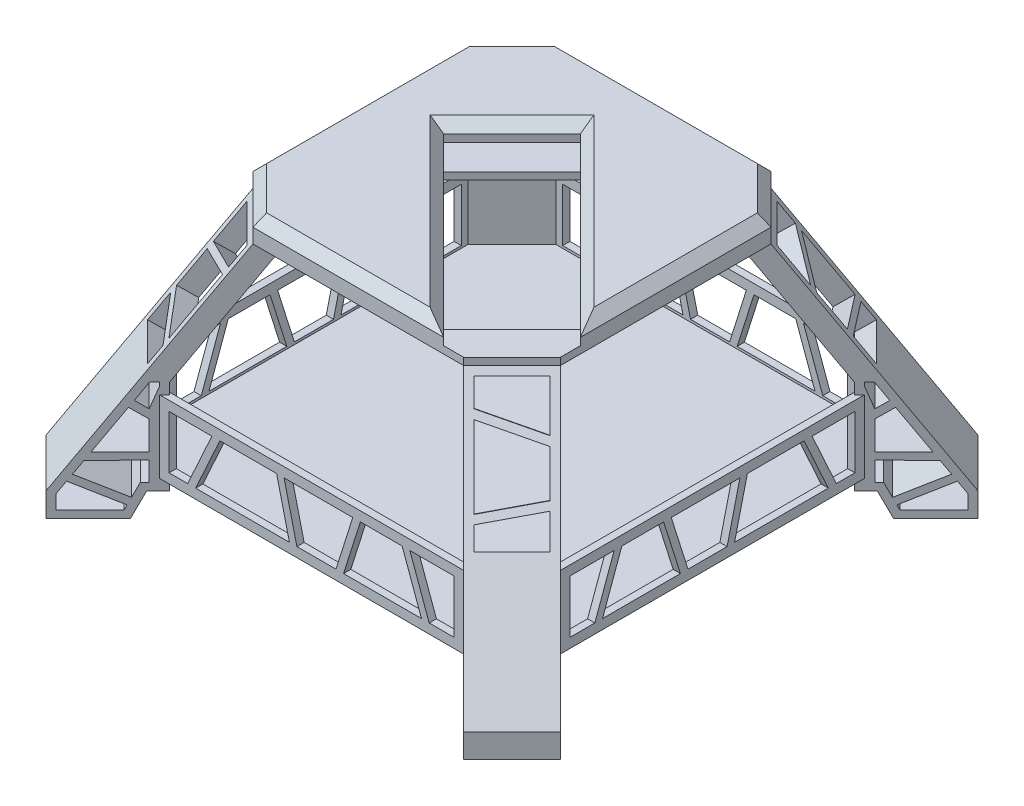
SolidWorks part; units mm, degrees
ref_plane "Front Plane" through (0, 0, 0) normal (0, 0, 1) x (1, 0, 0)
ref_plane "Top Plane" through (0, 0, 0) normal (0, 1, 0) x (1, 0, 0)
ref_plane "Right Plane" through (0, 0, 0) normal (1, 0, 0) x (0, 0, -1)
sketch "Sketch1" plane through (0, 0, 0) normal (0, 1, 0) x (1, 0, 0)
  line L0 (-31.5, 41.5) -> (-41.5, 31.5)
  line L1 (-31.5, 41.5) -> (31.5, 41.5)
  line L2 (-41.5, 31.5) -> (-41.5, -31.5)
  line L3 (-31.5, -41.5) -> (31.5, -41.5)
  line L4 (41.5, 31.5) -> (41.5, -31.5)
  line L5 (-41.5, 41.5) -> (41.5, -41.5) construction
  line L6 (-41.5, -41.5) -> (41.5, 41.5) construction
  line L7 (31.5, 41.5) -> (41.5, 31.5)
  line L8 (41.5, -31.5) -> (31.5, -41.5)
  line L9 (-41.5, -31.5) -> (-31.5, -41.5)
  point P0 (0, 0)
  point P14 (40, -37.4819)
  dimension "D1" = 83
extrude "Boss-Extrude1" add sketch "Sketch1" along normal blind 15
shell "Shell1" thickness 1.5 removed face at (0, 15, 0)
ref_plane "Plane1" through (0, 0, 0) normal (-0.7071, 0, 0.7071) x (0.7071, 0, 0.7071)
sketch "Sketch15" plane through (41.5, 0, 0) normal (1, 0, 0) x (0, 0, -1)
  line L0 (18.9934, 13) -> (7.2371, 13)
  line L1 (25.6494, 2) -> (29.5, 2)
  line L4 (-24.3478, 2) -> (-20.3494, 13)
  line L5 (-22.7518, 2) -> (-18.7534, 13)
  line L6 (-10.1007, 13) -> (-6.6274, 2)
  line L7 (-8.5277, 13) -> (-5.0544, 2)
  line L8 (-29.5, 2) -> (29.5, 2)
  line L9 (29.5, 2) -> (29.5, 13)
  line L10 (29.5, 13) -> (-29.5, 13)
  line L11 (-29.5, 13) -> (-29.5, 2)
  line L12 (-29.5, 2) -> (-24.3478, 2)
  line L13 (29.5, 2) -> (29.5, 13)
  line L14 (29.5, 13) -> (20.6415, 13)
  line L15 (-29.5, 13) -> (-29.5, 2)
  line L16 (5.6941, 13) -> (3.0427, 2)
  line L17 (7.2371, 13) -> (4.5856, 2)
  line L18 (20.6415, 13) -> (25.6494, 2)
  line L19 (18.9934, 13) -> (24.0013, 2)
  line L20 (-10.1007, 13) -> (-18.7534, 13)
  line L21 (-5.0544, 2) -> (3.0427, 2)
  line L22 (-22.7518, 2) -> (-6.6274, 2)
  line L23 (-20.3494, 13) -> (-29.5, 13)
  line L24 (5.6941, 13) -> (-8.5277, 13)
  line L25 (4.5856, 2) -> (24.0013, 2)
  point P20 (-22.805, 13.5)
  point P21 (-12.8485, 13.5)
  point P22 (-18.7519, 13.5)
  point P23 (-6.6279, 1.5)
  point P24 (2.6342, 1.5)
  point P25 (7.646, 13.5)
  point P26 (24.2021, 1.5)
  point P27 (16.3093, 13.5)
  point P28 (-10.1007, 13)
  point P29 (5.6941, 13)
  point P30 (20.6415, 13)
  dimension "D2" = 1.5
  dimension "D3" = 1.5
  dimension "D4" = 1.5
  dimension "D5" = 1.5
extrude "Cut-Extrude3" cut sketch "Sketch15" against normal through all
mirror "Mirror4" about plane through (0, 0, 0) normal (-0.7071, 0, 0.7071) of "Cut-Extrude3"
sketch "Sketch2" plane through (0, 0, 0) normal (-0.7071, 0, 0.7071) x (0.7071, 0, 0.7071)
  line L8 (51.6188, 15) -> (50.1188, 15)
  line L9 (7.0711, 15) -> (51.6188, 15) construction
  line L10 (50.1188, 15) -> (50.1188, 17.2822)
  line L11 (50.1188, 17.2822) -> (54.873, 17.2822)
  line L12 (54.873, 17.2822) -> (68.2293, -2.2291)
  line L13 (68.2293, -2.2291) -> (68.2293, -7.1547)
  line L15 (68.2293, -7.1547) -> (55.8508, -7.1547)
  line L16 (55.8508, -7.1547) -> (53.4827, -2.2291)
  line L17 (53.4827, -2.2291) -> (50.1188, -2.2291)
  line L18 (50.1188, -2.2291) -> (50.1188, 0)
  line L19 (7.0711, 0) -> (51.6188, 0) construction
  line L20 (50.1188, 0) -> (51.6188, 0)
  line L21 (51.6188, 0) -> (51.6188, 15)
  point P2 (64.5609, -7.0719)
  point P3 (62.5346, -7.0719)
  point P6 (56.9209, -7.2687)
  point P10 (0, 0)
  point P21 (52.5181, -4.5307)
  point P22 (0, 0)
  point P23 (78.9484, -7.599)
  point P24 (57.923, -7.599)
  point P25 (68.246, 13.75)
  point P26 (71.077, 1.0103)
  point P27 (69.9761, 12.649)
  point P28 (77.9974, 1.3248)
  point P29 (77.9974, -7.9547)
  point P30 (50.7878, -12.044)
  point P31 (57.5509, -13.3023)
  point P32 (58.6405, 20.9849)
  point P33 (75.6382, 12.1772)
  point P34 (75.6382, -7.4459)
  point P35 (54.248, -3.7082)
  point P36 (74.7081, 6.8297)
  point P37 (61.6402, -7.4459)
  point P38 (58.0112, -3.0389)
  point P39 (0, 0)
  point P40 (0, 0)
  point P41 (46.258, 21.307)
  point P42 (65.0866, -7.4459)
  point P43 (74.3882, -0.0167)
  point P44 (48.0794, 15)
  point P45 (48.755, 15)
  point P46 (48.1238, 15)
  point P47 (0, 0)
  point P49 (48.2026, -0.5309)
  point P50 (54.4571, -7.4459)
  point P51 (51.287, -5.6451)
  point P52 (51.8837, -7.4459)
  point P53 (74.2619, -4.6657)
  point P54 (53.5036, -8.1413)
  point P55 (51.6286, -3.6276)
  point P56 (54.0935, -7.4459)
  point P57 (50.1188, 16.8913)
  point P58 (62.3577, -7.4459)
  point P59 (70.8334, -2.7865)
  point P60 (70.8334, -7.4459)
  point P61 (61.9116, -7.4459)
  point P62 (55.5176, -1.8943)
  point P63 (57.5224, -7.4459)
  point P64 (0, 0)
  point P65 (55.8508, -7.1547)
  point P66 (53.4827, -2.2291)
  point P67 (68.2293, -7.1547)
  point P68 (68.2293, -2.2291)
  point P69 (54.873, 17.2822)
extrude "Boss-Extrude2" add sketch "Sketch2" along normal up to vertex (7.0711 mm away) and the other way up to vertex (7.0711 mm away) separate body up to point (31.5, 15, 41.5) other way up to point (41.5, 15, 31.5)
sketch "Sketch6" plane through (0, 17.2822, 0) normal (0, 1, 0) x (1, 0, 0)
  line L4 (33.8011, -43.8011) -> (43.8011, -33.8011)
  line L5 (43.8011, -33.8011) -> (40.4393, -30.4393)
  line L6 (40.4393, -30.4393) -> (30.4393, -40.4393)
  line L7 (30.4393, -40.4393) -> (33.8011, -43.8011)
  line L8 (33.8011, -43.8011) -> (43.8011, -33.8011)
  line L9 (43.8011, -33.8011) -> (40.4393, -30.4393)
  line L10 (40.4393, -30.4393) -> (30.4393, -40.4393)
  line L11 (30.4393, -40.4393) -> (33.8011, -43.8011)
  dimension "D1" = 0
extrude "Boss-Extrude4" add sketch "Sketch6" along direction (-0.3994, 0.8252, -0.3994) on the side of the normal blind 30
sketch "Sketch8" plane through (32.1166, 31.0918, 32.1166) normal (0.5835, 0.5649, 0.5835) x (0.809, -0.4673, -0.3566)
  line L0 (1.1, -11.4379) -> (3.3653, -14.7346)
  line L1 (8.2873, -2.2233) -> (3.7894, 4.3224)
  line L2 (2.8883, 5.6338) -> (-2.0712, 12.8513)
  line L3 (-7.6275, 1.2631) -> (0.2369, -10.1819)
  line L4 (-8.5286, 2.5745) -> (2.8883, 5.6338)
  line L5 (-7.6275, 1.2631) -> (3.7894, 4.3224)
  line L6 (0.2369, -10.1819) -> (8.2873, -2.2233)
  line L7 (1.1, -11.4379) -> (9.1504, -3.4793)
  line L8 (17.4277, -35.1992) -> (26.6107, -28.889)
  line L9 (26.6107, -28.889) -> (-2.0712, 12.8513)
  line L10 (-2.0712, 12.8513) -> (-11.2543, 6.5411)
  line L11 (-11.2543, 6.5411) -> (17.4277, -35.1992)
  line L14 (-2.0712, 12.8513) -> (-11.2543, 6.5411)
  line L15 (-11.2543, 6.5411) -> (-8.5286, 2.5745)
  line L16 (3.3653, -14.7346) -> (12.5484, -8.4244)
  line L19 (12.5484, -8.4244) -> (9.1504, -3.4793)
  line L21 (2.1291, -15.5841) -> (13.7847, -7.5749) construction
  line L22 (28.6965, -29.2758) -> (-1.6845, 14.937) construction
  point P16 (2.1734, -12.9999)
  point P17 (6.605, 0)
  point P18 (0, -10.2448)
  point P19 (0, -9.8778)
  point P20 (-1.1516, -8.1612)
  point P21 (14.8221, -11.7333)
  point P22 (-0.3439, -9.3366)
  point P23 (11.3401, -6.666)
  point P24 (8.0094, -1.8258)
  point P25 (-6.2966, -0.6737)
  point P26 (3.8328, 4.3953)
  point P27 (-1.6692, -7.4079)
  point P28 (-1.1778, -8.4136)
  point P29 (6.7209, 0)
  point P30 (11.6875, -7.0916)
  point P31 (1.1073, -11.6826)
  point P32 (10.7464, -5.802)
  point P33 (-1.0138, -8.3617)
  point P34 (0, -10.2259)
  point P35 (9.8852, -4.5487)
  point P36 (-1.0881, -8.2535)
  point P37 (6.7776, -0.7438)
  point P38 (-0.2205, -9.5162)
  point P39 (11.7055, -7.2554)
  point P42 (8.3861, -2.3671)
  point P43 (-0.2959, -9.4064)
  point P44 (7.4734, -1.0389)
  point P45 (-0.457, -9.1721)
  point P46 (0.3662, -10.37)
  point P47 (-4.6581, -3.0582)
  point P48 (-5.069, -2.4602)
  point P49 (8.869, -3.0698)
  point P50 (0, -9.9183)
  point P51 (-4.8635, -2.7592)
  point P52 (0, -10.0166)
  point P53 (0.8274, -11.0411)
  point P54 (-4.3269, -3.5402)
  point P55 (6.729, 0)
  point P56 (-3.4368, -4.8355)
  point P57 (-4.3047, -3.5726)
  point P58 (6.246, 0.7473)
  point P59 (-3.5397, -4.8949)
  point P60 (-3.4368, -4.8355)
  point P61 (-4.3071, -3.569)
  point P62 (-4.4936, -3.2885)
  point P63 (5.4459, 1.9117)
  point P64 (-7.6565, 1.3053)
  point P65 (4.2592, 3.6387)
  point P66 (3.7894, 4.3224)
  point P67 (-7.6275, 1.2631)
  dimension "D2" = 1.5
  dimension "D3" = 1.5
  dimension "D4" = 4
  dimension "D5" = 6
  dimension "D1" = 1.5
extrude "Cut-Extrude1" cut sketch "Sketch8" against normal up to surface (3.9231 mm away) contours L14 L15 L4 L2 | L3 L6 L1 L5 | L16 L19 L7 L0 region at (36.9792, 21.5887, 36.4539) region at (32.5676, 29.4212, 33.2828) region at (29.1924, 37.9215, 28.429) up to face at (29.448, 29.6599, 29.448)
sketch "Sketch12" plane through (-5, 0, 5) normal (-0.7071, 0, 0.7071) x (0.7071, 0, 0.7071)
  line L1 (56.3607, -4.7534) -> (65.2229, -0.4927)
  line L2 (54.8346, -1.5792) -> (57.2026, -6.5047)
  line L3 (56.3607, -4.7534) -> (56.794, -5.6547)
  line L55 (51.6188, 17.2822) -> (53.0552, 17.2822)
  line L56 (53.1188, 12.4783) -> (55.3147, 13.9814)
  line L57 (53.1188, 10.6605) -> (56.162, 12.7437)
  line L58 (53.1188, 4.7709) -> (61.6416, 4.7389)
  line L59 (53.1188, 3.2709) -> (62.6711, 3.235)
  line L60 (55.7107, -3.4015) -> (64.3657, 0.7595)
  line L62 (53.1188, 10.6605) -> (53.1188, 4.7709)
  line L63 (55.3147, 13.9814) -> (53.0552, 17.2822)
  line L64 (53.1188, 3.2709) -> (53.1188, -0.7291)
  line L65 (66.7293, -2.6933) -> (36.6891, 41.1902)
  line L66 (66.7293, -5.6547) -> (66.7293, -2.6933)
  line L67 (56.794, -5.6547) -> (66.7293, -5.6547)
  line L68 (54.4259, -0.7291) -> (56.794, -5.6547)
  line L69 (51.6188, 16.5) -> (53.1188, 16.5)
  line L70 (51.6188, 17.2822) -> (51.6188, 16.5)
  line L71 (53.1188, 16.5) -> (53.1188, -0.7291)
  line L72 (53.1188, -0.7291) -> (54.4259, -0.7291)
  line L73 (66.7293, -2.6933) -> (65.2229, -0.4927)
  line L74 (66.7293, -5.6547) -> (66.7293, -2.6933)
  line L75 (56.794, -5.6547) -> (66.7293, -5.6547)
  line L76 (54.4259, -0.7291) -> (55.7107, -3.4015)
  line L78 (51.6188, 17.2822) -> (51.6188, 16.5)
  line L80 (53.1188, -0.7291) -> (54.4259, -0.7291)
  line L81 (61.6416, 4.7389) -> (56.162, 12.7437)
  line L82 (64.3657, 0.7595) -> (62.6711, 3.235)
  line L83 (51.6188, 16.5) -> (53.1188, 12.4783)
  point P10 (58.39, -4.7753)
  point P14 (68.2214, -1.6023)
  point P15 (64.7943, 3.4641)
  dimension "D2" = 1.5
  dimension "D3" = 1.5
  dimension "D1" = 1.5
  dimension "D5" = 4
  dimension "D6" = 3
  dimension "D8" = 4
  dimension "D9" = 1.5
  dimension "D7" = 1
  dimension "D4" = 1.5
extrude "Cut-Extrude2" cut sketch "Sketch12" against normal up to next (14.1421 mm away)
ref_plane "Plane2" through (0, 0, 0) normal (-1, 0, 0) x (0, 0, 1)
ref_plane "Plane3" through (0, 0, 0) normal (0, 0, -1) x (-1, 0, 0)
mirror "Mirror1" about plane through (0, 0, 0) normal (-1, 0, 0) of bodies 114 102
mirror "Mirror2" about plane through (0, 0, 0) normal (0, 0, -1) of bodies 103 114 102
ref_axis "Axis1" through (0, 0, 0) along (0, 1, 0)
sketch "Sketch7" plane through (0, 42.0375, 0) normal (0, 1, 0) x (1, 0, 0)
  line L0 (-31.8183, -21.8183) -> (-31.8183, 21.8183)
  line L1 (-31.8183, 21.8183) -> (-21.8183, 31.8183)
  line L2 (-21.8183, 31.8183) -> (21.8183, 31.8183)
  line L3 (21.8183, 31.8183) -> (31.8183, 21.8183)
  line L4 (31.8183, 21.8183) -> (31.8183, -21.8183)
  line L5 (31.8183, -21.8183) -> (21.8183, -31.8183)
  line L6 (21.8183, -31.8183) -> (-21.8183, -31.8183)
  line L7 (-21.8183, -31.8183) -> (-31.8183, -21.8183)
  line L8 (-18.809, 4.6669) -> (-4.6669, 18.809)
  line L9 (-4.6669, 18.809) -> (34.224, -20.0818)
  line L10 (34.224, -20.0818) -> (20.0818, -34.224)
  line L11 (20.0818, -34.224) -> (-18.809, 4.6669)
  line L12 (14.7785, -28.9207) -> (28.9207, -14.7785)
  line L13 (28.9207, -14.7785) -> (0.6364, 13.5057)
  line L14 (0.6364, 13.5057) -> (-13.5057, -0.6364)
  line L15 (-11.738, 11.738) -> (27.1529, -27.1529) construction
  circle A0 centre (0, 0) radius 4.2245
  point P26 (34.5378, -19.5372)
  point P27 (14.7785, -0.6364)
  point P28 (14.7785, -0.6364)
  point P32 (20.0818, -34.224)
  line M8 (18.4566, -28.4566) -> (21.8183, -31.8183)
  line M9 (21.8183, -31.8183) -> (31.8183, -21.8183)
  line M10 (31.8183, -21.8183) -> (28.4566, -18.4566)
  dimension "D1" = 20
  dimension "D2" = 55
  dimension "D3" = 40
  dimension "D4" = 16.6
extrude "Boss-Extrude5" add sketch "Sketch7" along normal blind 5 contours L6 L11 L8 L9 L4 L3 L2 L1 L0 L7 region at (-30.9184, 42.0375, 0)
extrude "Boss-Extrude6" add sketch "Sketch7<3>" along normal blind 1.5 contours L8 L15 L14 L9 | L15 L8 L11 L14 | L15 L12 M8 M9 | L12 L11 L6 M8 | L12 L15 L5 M10 | L12 L4 L9 M10 region at (20.8668, 42.0375, 27.5679) region at (27.5679, 42.0375, 20.8668) region at (-12.6219, 42.0375, -5.5508) region at (-5.5508, 42.0375, -12.6219)
sketch "Sketch7<3>" plane through (0, 42.0375, 0) normal (0, 1, 0) x (1, 0, 0) same geometry as "Sketch7"
chamfer "Chamfer1" distance 2 angle 45 10 edges at (-26.8183, 47.0375, 26.8183) (-31.8183, 47.0375, 0) (-26.8183, 47.0375, -26.8183) (0, 47.0375, -31.8183) (26.8183, 47.0375, -26.8183) (31.8183, 47.0375, -2.0711) (13.5757, 47.0375, -0.5664) (-11.738, 47.0375, -11.738) (-0.5664, 47.0375, 13.5757) (-2.0711, 47.0375, 31.8183)
sketch "Sketch16" plane through (0, 0, 0) normal (0, 0, -1) x (-1, 0, 0)
  line L0 (-41.5, 15) -> (-43.9015, 15)
  line L1 (-43.9015, 15) -> (-51.7285, 0)
  line L2 (-51.7285, 0) -> (-41.5, 0)
  line L3 (-41.5, 0) -> (-41.5, 15)
  point P2 (0, 0)
  point P6 (-41.7571, 0)
  point P9 (-51.7285, 0)
equation "\"D3@Sketch8\"=\"D2@Sketch8\""
equation "\"D2@Sketch12\"=\"D1@Sketch12\""
equation "\"D3@Sketch12\"=\"D2@Sketch12\""
equation "\"D3@Sketch15\"=\"D2@Sketch15\""
equation "\"D4@Sketch15\"=\"D3@Sketch15\""
